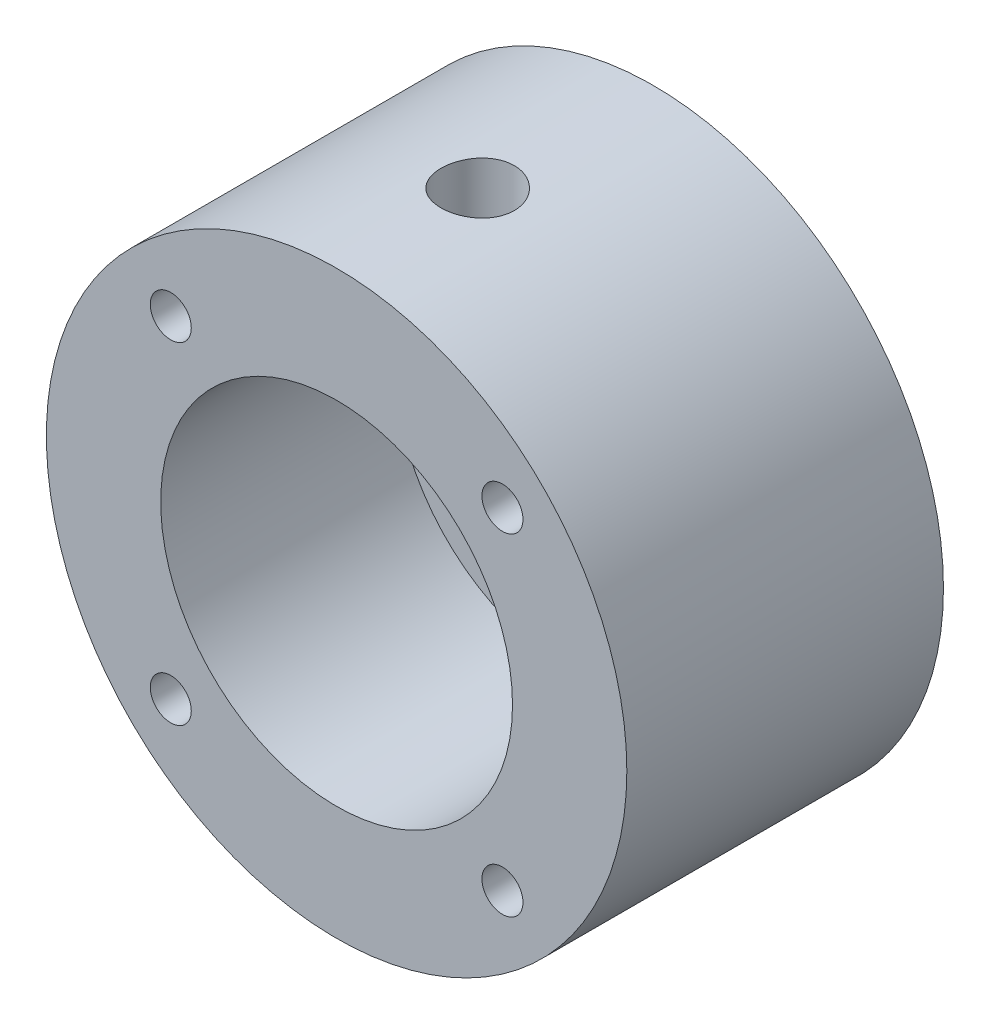
SolidWorks part; units mm, degrees
ref_plane "Front Plane" through (0, 0, 0) normal (0, 0, 1) x (1, 0, 0)
ref_plane "Top Plane" through (0, 0, 0) normal (0, 1, 0) x (1, 0, 0)
ref_plane "Right Plane" through (0, 0, 0) normal (1, 0, 0) x (0, 0, -1)
sketch "Sketch1" plane through (0, 0, 0) normal (0, 0, 1) x (1, 0, 0)
  circle A0 centre (0, 0) radius 12.573
  dimension "D1" = 25.146
extrude "Boss-Extrude1" add sketch "Sketch1" along normal blind 13.716
sketch "Sketch2" plane through (0, 0, 13.716) normal (0, 0, 1) x (1, 0, 0)
  circle A0 centre (0, 0) radius 7.62
  dimension "D1" = 15.24
extrude "Cut-Extrude1" cut sketch "Sketch2" against normal blind 10.16 contours A0
ref_plane "Plane1" through (0, 0, 7.62) normal (0, 0, -1) x (-1, 0, 0)
sketch "Sketch5" plane through (0, 0, 7.62) normal (0, 0, -1) x (-1, 0, 0)
  line L1 (-4.6994, 1.996) -> (4.2606, 1.996)
  line L2 (1.5, 1.996) -> (-1.5, 1.996)
  line L3 (-4.6994, 1.996) -> (-4.6994, -3.714)
  line L4 (-4.6994, -3.714) -> (4.2606, -3.714)
  line L5 (4.2606, 1.996) -> (4.2606, -3.714)
  circle A0 centre (0, -0.004) radius 12.573
  circle A1 centre (0, -0.004) radius 2.5
  point P3 (0, 12.569)
  dimension "D1" = 25.146
  dimension "D2" = 5
ref_plane "Plane2" through (0, 12.573, 7.62) normal (0, 1, 0) x (1, 0, 0)
sketch "Sketch10" plane through (0, 12.573, 7.62) normal (0, 1, 0) x (1, 0, 0)
  point P0 (0, 0.0143)
hole_wizard "1/8 (0.1250) Dowel Hole1" positions "Sketch12" profile "Sketch11" hole size "1/8" standard "ANSI Inch" end condition up to next
sketch "Sketch12" plane through (0, 12.573, 7.62) normal (0, 1, 0) x (1, 0, 0)
  point P0 (0, 0.0143)
sketch "Sketch11" plane through (0, 12.573, 7.6057) normal (1, 0, 0) x (0, 0, 1)
  line L0 (0, 0) -> (0, 4.953)
  line L1 (0, 4.953) -> (1.5875, 4.953)
  line L2 (1.5875, 4.953) -> (1.5875, 0)
  line L5 (1.5875, 0) -> (0, 0)
  line L11 (0, -6.35) -> (0, 107.95) construction
  dimension "Thru Hole Dia." = 3.175
  dimension "Thru Hole Depth" = 4.953
extrude "Cut-Extrude3" cut sketch "Sketch5" against normal blind 10.16 and the other way blind 10 contours L1 A1 region at (0, -0.1249, 7.62)
sketch "Sketch14" plane through (0, 0, 13.716) normal (0, 0, 1) x (1, 0, 0)
  circle A0 centre (0, -0.004) radius 10.16
  point P5 (10.16, -0.004)
  point P7 (7.1842, -7.1882)
  point P8 (0, -0.004)
  dimension "D1" = 20.32
  dimension "D2" = 2
hole_wizard "#2-56 Tapped Hole1" positions "Sketch16" profile "Sketch15" tap size "#2-56" standard "ANSI Inch"
sketch "Sketch16" plane through (0, 0, 13.716) normal (0, 0, 1) x (1, 0, 0)
  point P0 (7.1842, -7.1882)
sketch "Sketch15" plane through (7.1842, -7.1882, 13.716) normal (1, 0, 0) x (0, -1, 0)
  line L0 (0, 0) -> (0, 8.2481)
  line L1 (0, 8.2481) -> (0.889, 7.714)
  line L2 (0.889, 7.714) -> (0.889, 0)
  line L5 (0.889, 0) -> (0, 0)
  line L10 (0, 8.2481) -> (-0.889, 7.714) construction
  line L11 (0, -6.35) -> (0, 107.95) construction
  dimension "Tap Drill Dia." = 1.778
  dimension "Tap Drill Depth" = 7.714
  dimension "Drill Angle" = 118
cosmetic thread "Hole Thread1" parameters "D1"=6.35, "D2"=2.1844
ref_axis "Axis1" through (0, -0.004, 13.716) along (0, 0, 1)
pattern_circular "CirPattern1" count 4 every 90 about axis through (0, -0.004, 13.716) along (0, 0, 1) of "#2-56 Tapped Hole1"
